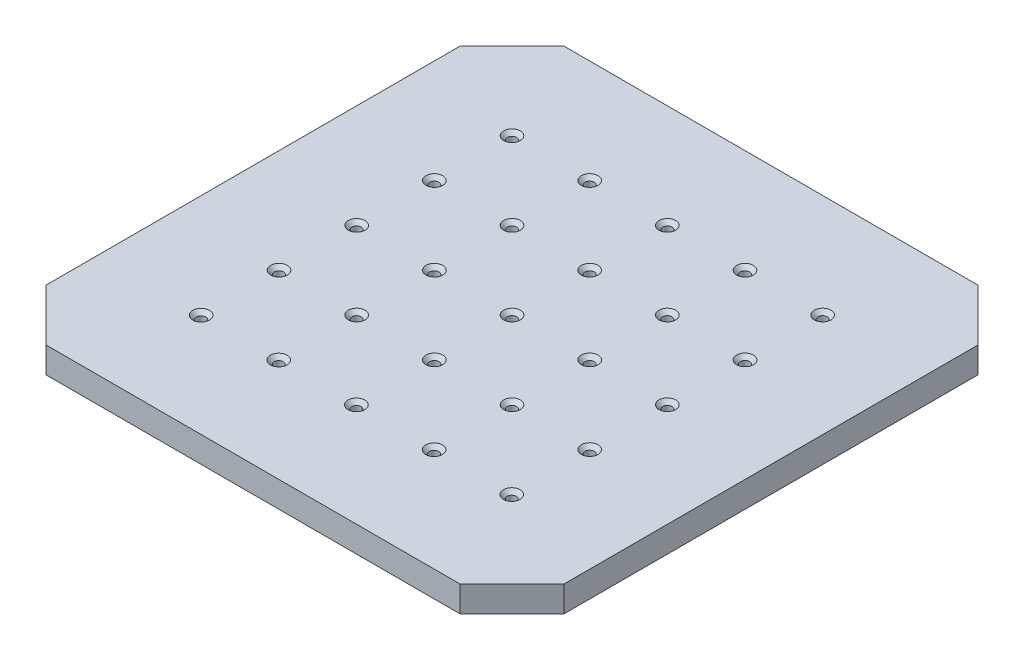
SolidWorks part; units mm, degrees
ref_plane "Front Plane" through (0, 0, 0) normal (0, 0, 1) x (1, 0, 0)
ref_plane "Top Plane" through (0, 0, 0) normal (0, 1, 0) x (1, 0, 0)
ref_plane "Right Plane" through (0, 0, 0) normal (1, 0, 0) x (0, 0, -1)
sketch "Sketch1" plane through (0, 0, 0) normal (0, 1, 0) x (1, 0, 0)
  line L1 (63.5, -63.5) -> (-63.5, -63.5)
  line L2 (63.5, -63.5) -> (63.5, 63.5)
  line L3 (63.5, 63.5) -> (-63.5, 63.5)
  line L4 (-63.5, -63.5) -> (-63.5, 63.5)
  line L5 (63.5, -63.5) -> (-63.5, 63.5) construction
  line L6 (63.5, 63.5) -> (-63.5, -63.5) construction
  point P0 (0, 0)
  dimension "D1" = 127
  dimension "D2" = 127
extrude "Boss-Extrude1" add sketch "Sketch1" along normal blind 6.35
sketch "Sketch4" plane through (0, 0, 0) normal (0, 1, 0) x (1, 0, 0)
  line L0 (0, 63.5) -> (0, -63.5)
  line L1 (63.5, 63.5) -> (-63.5, 63.5) construction
  line L2 (-63.5, -63.5) -> (63.5, -63.5) construction
  line L3 (-63.5, 0) -> (63.5, 0)
  line L4 (-63.5, 63.5) -> (-63.5, -63.5) construction
  line L5 (63.5, -63.5) -> (63.5, 63.5) construction
sketch "Sketch5" plane through (0, 0, 0) normal (0, 1, 0) x (1, 0, 0)
  line L0 (-63.5, 0) -> (63.5, 0) construction
  line L1 (0, 63.5) -> (0, -63.5) construction
  point P0 (0, 0)
  point P1 (-19.05, 0)
  point P3 (19.05, 0)
  point P6 (38.1, 0)
  point P7 (-38.1, 0)
  point P8 (0, 19.05)
  point P9 (0, 38.1)
  point P12 (0, -19.05)
  point P13 (0, -38.1613)
  point P14 (19.05, -19.05)
  point P15 (19.05, -38.1613)
  point P16 (38.1, -38.1613)
  point P17 (38.1, -19.05)
  point P18 (-19.05, -19.05)
  point P19 (-19.05, -38.1613)
  point P20 (-38.1, -38.1613)
  point P21 (-38.1, -19.05)
  point P22 (-19.05, 19.05)
  point P23 (-38.1, 19.05)
  point P24 (-38.1, 38.1)
  point P25 (-19.05, 38.1)
  point P26 (19.05, 38.1)
  point P27 (19.05, 19.05)
  point P28 (38.1, 19.05)
  point P29 (38.1, 38.1)
  point P31 (0, 0)
sketch "Sketch11" plane through (0, 6.35, 0) normal (0, 1, 0) x (1, 0, 0)
  line L0 (-63.5, 0) -> (63.5, 0) construction
  point P0 (19.05, 0)
  point P3 (0, 0)
  point P6 (0, -19.05)
  point P9 (-19.05, -19.05)
  point P12 (-38.1, -19.05)
  point P15 (-38.1, -38.1613)
  point P18 (-19.05, -38.1613)
  point P21 (0, -38.1613)
  point P24 (19.05, -38.1613)
  point P27 (19.05, -19.05)
  point P30 (38.1, -19.05)
  point P33 (38.1, -38.1613)
  point P36 (38.1, 0)
  point P39 (0, 0)
  point P43 (-19.05, 0)
  point P46 (-38.1, 0)
  point P49 (-38.1, 19.05)
  point P52 (-19.05, 19.05)
  point P55 (0, 19.05)
  point P58 (19.05, 19.05)
  point P61 (38.1, 19.05)
  point P64 (0, 38.1)
  point P67 (19.05, 38.1)
  point P70 (38.1, 38.1)
  point P73 (-19.05, 38.1)
  point P76 (-38.1, 38.1)
hole_wizard "#4-40 Tapped Hole2" positions "Sketch11" profile "Sketch10" tap size "#4-40" standard "ANSI Inch" end condition through all
sketch "Sketch10" plane through (19.05, 6.35, 0) normal (1, 0, 0) x (0, 0, 1)
  line L0 (0, 0) -> (0, 6.35)
  line L1 (0, 6.35) -> (1.1303, 6.35)
  line L2 (1.1303, 6.35) -> (1.1303, 0.9271)
  line L3 (1.1303, 0.9271) -> (2.0574, 0)
  line L5 (2.0574, 0) -> (0, 0)
  line L6 (-1.1303, 0.9271) -> (-2.0574, 0) construction
  line L11 (0, -6.35) -> (0, 107.95) construction
  dimension "Thru Tap Drill Dia." = 2.2606
  dimension "Thru Tap Drill Depth" = 6.35
  dimension "Near C'Sink Dia." = 4.1148
  dimension "Near C'Sink Angle" = 90
cosmetic thread "Hole Thread26" parameters "D2"=2.8448
cosmetic thread "Hole Thread27" parameters "D2"=2.8448
cosmetic thread "Hole Thread28" parameters "D2"=2.8448
cosmetic thread "Hole Thread29" parameters "D2"=2.8448
cosmetic thread "Hole Thread30" parameters "D2"=2.8448
cosmetic thread "Hole Thread31" parameters "D2"=2.8448
cosmetic thread "Hole Thread32" parameters "D2"=2.8448
cosmetic thread "Hole Thread33" parameters "D2"=2.8448
cosmetic thread "Hole Thread34" parameters "D2"=2.8448
cosmetic thread "Hole Thread35" parameters "D2"=2.8448
cosmetic thread "Hole Thread36" parameters "D2"=2.8448
cosmetic thread "Hole Thread37" parameters "D2"=2.8448
cosmetic thread "Hole Thread39" parameters "D2"=2.8448
cosmetic thread "Hole Thread40" parameters "D2"=2.8448
cosmetic thread "Hole Thread41" parameters "D2"=2.8448
cosmetic thread "Hole Thread42" parameters "D2"=2.8448
cosmetic thread "Hole Thread43" parameters "D2"=2.8448
cosmetic thread "Hole Thread44" parameters "D2"=2.8448
cosmetic thread "Hole Thread45" parameters "D2"=2.8448
cosmetic thread "Hole Thread46" parameters "D2"=2.8448
cosmetic thread "Hole Thread47" parameters "D2"=2.8448
cosmetic thread "Hole Thread48" parameters "D2"=2.8448
cosmetic thread "Hole Thread49" parameters "D2"=2.8448
cosmetic thread "Hole Thread50" parameters "D2"=2.8448
cosmetic thread "Hole Thread51" parameters "D2"=2.8448
fillet "Chamfer3" radius 12.7 1 edges at (-63.5, 3.175, 63.5) type face fillet profile chamfer first side face at (0, 3.175, 63.5) second side face at (-63.5, 3.175, 0)
fillet "Chamfer4" radius 12.7 1 edges at (63.5, 3.175, 63.5) type face fillet profile chamfer first side face at (6.35, 3.175, 63.5) second side face at (63.5, 3.175, 0)
fillet "Chamfer5" radius 12.7 1 edges at (63.5, 3.175, -63.5) type face fillet profile chamfer first side face at (63.5, 3.175, -6.35) second side face at (0, 3.175, -63.5)
fillet "Chamfer6" radius 12.7 1 edges at (-63.5, 3.175, -63.5) type face fillet profile chamfer first side face at (-63.5, 3.175, -6.35) second side face at (-6.35, 3.175, -63.5)
